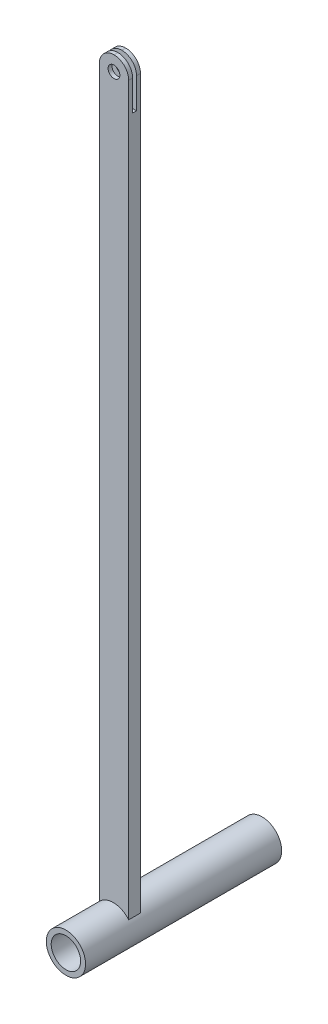
SolidWorks part; units mm, degrees
ref_plane "前视基准面" through (0, 0, 0) normal (0, 0, 1) x (1, 0, 0)
ref_plane "上视基准面" through (0, 0, 0) normal (0, 1, 0) x (1, 0, 0)
ref_plane "右视基准面" through (0, 0, 0) normal (1, 0, 0) x (0, 0, -1)
sketch "草图1" plane through (0, 0, 0) normal (0, 0, 1) x (1, 0, 0)
  circle A0 centre (0, 0) radius 10
  circle A1 centre (0, 0) radius 7.5
  dimension "D1" = 20
  dimension "D2" = 15
extrude "凸台-拉伸1" add sketch "草图1" along normal mid plane 100
ref_plane "基准面1" through (0, 384.51, 0) normal (0, 1, 0) x (1, 0, 0)
sketch "草图2" plane through (0, 384.51, 0) normal (0, 1, 0) x (1, 0, 0)
  line L1 (-7.219, -19.7798) -> (7.781, -19.7798)
  line L2 (-7.219, -19.7798) -> (-7.219, -25.7798)
  line L3 (-7.219, -25.7798) -> (7.781, -25.7798)
  line L4 (7.781, -19.7798) -> (7.781, -25.7798)
  line L5 (0.281, -25.7798) -> (0.281, -19.7798) construction
  line L6 (-7.219, -22.7798) -> (7.781, -22.7798) construction
  point P0 (0.281, 0)
  point P2 (0.281, -22.7798)
  dimension "D1" = 6
  dimension "D2" = 15
extrude "凸台-拉伸2" add sketch "草图2" against normal up to surface (378.2286 mm away) up to face at (10, 0, 50)
fillet "圆角1" radius 7.5 2 edges at (7.781, 384.51, 22.7798) (-7.219, 384.51, 22.7798)
sketch "草图3" plane through (0, 0, 19.7798) normal (0, 0, -1) x (-1, 0, 0)
  circle A0 centre (-0.281, 377.01) radius 3
  dimension "D1" = 6
extrude "切除-拉伸1" cut sketch "草图3" against normal blind 10
sketch "草图4" plane through (-7.219, 0, 0) normal (-1, 0, 0) x (0, 0, 1)
  line L0 (25.7798, 377.01) -> (19.7798, 377.01) construction
  line L1 (21.7798, 384.51) -> (23.7798, 384.51)
  line L2 (21.7798, 384.51) -> (21.7798, 361.51)
  line L3 (21.7798, 361.51) -> (23.7798, 361.51)
  line L4 (23.7798, 384.51) -> (23.7798, 361.51)
  line L5 (22.7798, 361.51) -> (22.7798, 384.51) construction
  line L6 (21.7798, 373.01) -> (23.7798, 373.01) construction
  line L7 (19.7798, 384.51) -> (25.7798, 384.51) construction
  line L8 (19.7798, 377.01) -> (25.7798, 377.01) construction
  point P0 (22.7798, 373.01)
  point P10 (22.7798, 377.01)
  dimension "D1" = 2
  dimension "D2" = 4
extrude "切除-拉伸2" cut sketch "草图4" against normal blind 20
